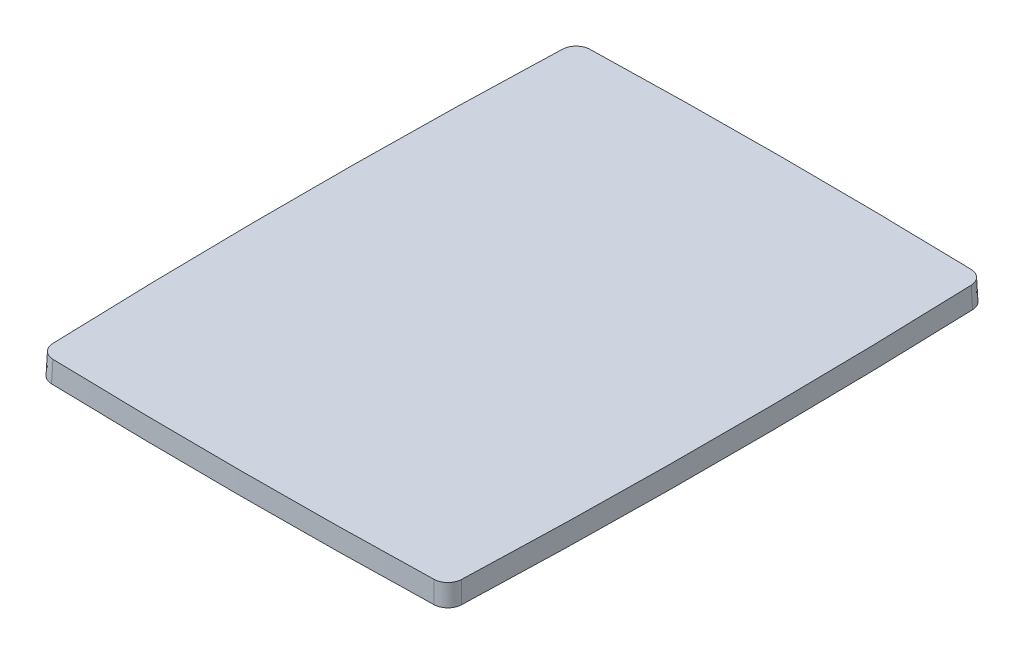
SolidWorks part; units mm, degrees
ref_plane "Front Plane" through (0, 0, 0) normal (0, 0, 1) x (1, 0, 0)
ref_plane "Top Plane" through (0, 0, 0) normal (0, 1, 0) x (1, 0, 0)
ref_plane "Right Plane" through (0, 0, 0) normal (1, 0, 0) x (0, 0, -1)
sketch "Sketch1" plane through (0, 0, 0) normal (0, 1, 0) x (1, 0, 0)
  line L0 (0, 0) -> (0, -500) construction
  line L1 (-13.8, 18.18) -> (13.8, 18.18) construction
  line L2 (-13.8, 18.18) -> (-13.8, -18.18) construction
  line L3 (-13.8, -18.18) -> (13.8, -18.18) construction
  line L4 (13.8, 18.18) -> (13.8, -18.18) construction
  line L5 (-13.8, 18.18) -> (13.8, -18.18) construction
  line L6 (-13.8, -18.18) -> (13.8, 18.18) construction
  line L7 (-14.8, 19.18) -> (14.8, 19.18) construction
  line L8 (-14.8, 19.18) -> (-14.8, -19.18) construction
  line L9 (-14.8, -19.18) -> (14.8, -19.18) construction
  line L10 (14.8, 19.18) -> (14.8, -19.18) construction
  line L11 (-14.8, 19.18) -> (14.8, -19.18) construction
  line L12 (-14.8, -19.18) -> (14.8, 19.18) construction
  line L13 (-18.8, 23.18) -> (18.8, 23.18) construction
  line L14 (-18.8, 23.18) -> (-18.8, -23.18) construction
  line L15 (-18.8, -23.18) -> (18.8, -23.18) construction
  line L16 (18.8, 23.18) -> (18.8, -23.18) construction
  line L17 (-18.8, 23.18) -> (18.8, -23.18) construction
  line L18 (-18.8, -23.18) -> (18.8, 23.18) construction
  line L19 (0, 0) -> (500, 0) construction
  line L20 (0, 0) -> (0, 53.4587) construction
  line L21 (0, 0) -> (-83.3147, 0) construction
  arc A4 (-14.4371, 18.9698) -> (-14.4371, -18.9698) centre (481.2, 0) ccw
  arc A7 (14.4371, 18.9698) -> (-14.4371, 18.9698) centre (0, -476.82) ccw
  arc A8 (14.4371, 18.9698) -> (14.4371, -18.9698) centre (-481.2, 0) cw
  arc A11 (14.4371, -18.9698) -> (-14.4371, -18.9698) centre (0, 476.82) cw
  point P0 (0, 0)
  point P6 (0, 0)
  point P11 (0, 0)
  dimension "D7" = 496
  dimension "D10" = 500
  dimension "D13" = 992
  dimension "D1" = 27.6
  dimension "D2" = 36.36
  dimension "D3" = 1
  dimension "D4" = 1
  dimension "D5" = 4
  dimension "D6" = 4
  dimension "D8" = 500
  dimension "D9" = 500
  dimension "D11" = 500
extrude "Boss-Extrude1" add sketch "Sketch1" along normal blind 1.5 draft 2
fillet "Fillet1" radius 1 4 edges
